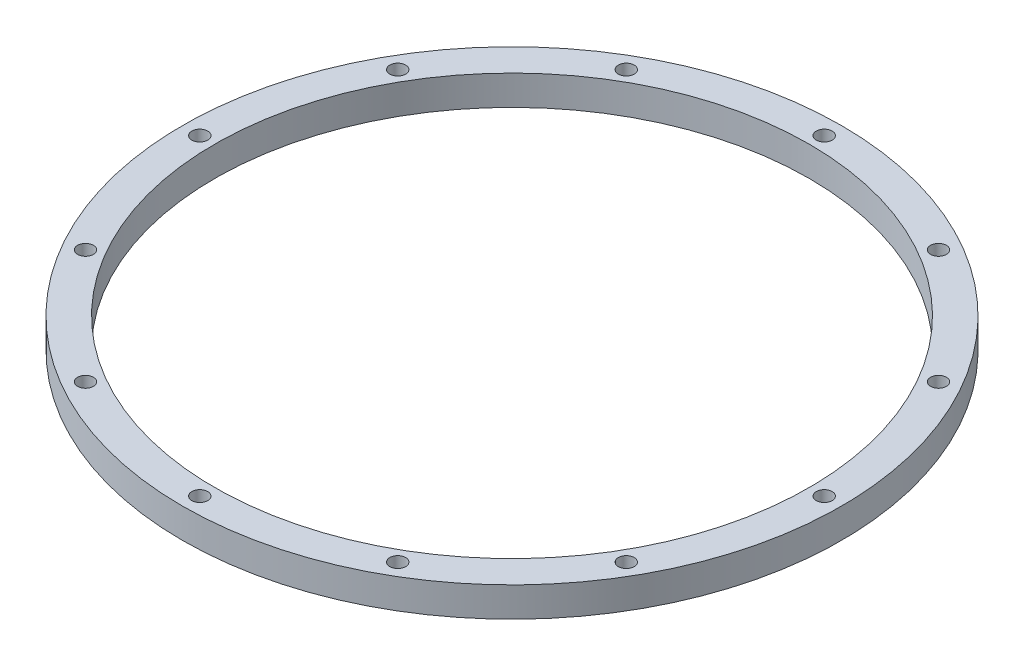
SolidWorks part; units mm, degrees
material "Hexcel AS4C (3000 Filaments)"
ref_plane "Front Plane" through (0, 0, 0) normal (0, 0, 1) x (1, 0, 0)
ref_plane "Top Plane" through (0, 0, 0) normal (0, 1, 0) x (1, 0, 0)
ref_plane "Right Plane" through (0, 0, 0) normal (1, 0, 0) x (0, 0, -1)
sketch "Sketch1" plane through (0, 0, 0) normal (0, 0, 1) x (1, 0, 0)
  line L0 (-60, 6.785) -> (-60, 0.785) construction
  line L1 (-66.5, 6.785) -> (-66.5, 0.785) construction
  line L2 (-60, 6.785) -> (-60, 0.785)
  line L3 (-66.5, 6.785) -> (-66.5, 0.785)
  line L4 (-60, 6.785) -> (-66.5, 6.785)
  line L5 (-60, 0.785) -> (-66.5, 0.785)
  line L6 (0, -200069.0475) -> (0, 200086.9028) construction
  line L7 (0, -200069.0475) -> (0, 200086.9028) construction
revolve "Revolve1" add sketch "Sketch1" angle 360 about L7
sketch "Sketch2" plane through (0, 6.785, 0) normal (0, 1, 0) x (1, 0, 0)
  circle A1 centre (0, 63) radius 1.6
  circle A2 centre (0, 63) radius 1.6
  dimension "D1" = 0
extrude "Cut-Extrude1" cut sketch "Sketch2" against normal through all
pattern_circular "CirPattern1" count 12 over 360 about axis through (0, -200069.0475, 0) along (0, -1, 0) of "Cut-Extrude1" reverse direction yes
